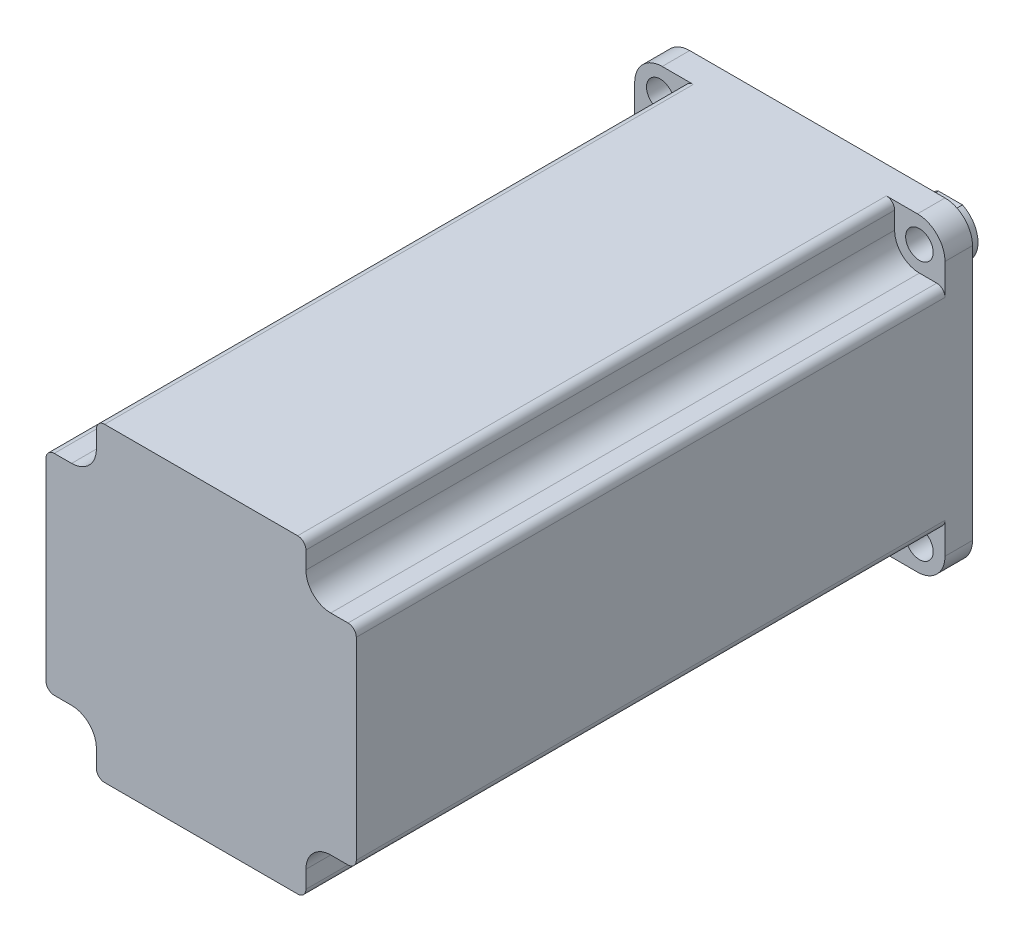
SolidWorks part; units mm, degrees
ref_plane "Front Plane" through (0, 0, 0) normal (0, 0, 1) x (1, 0, 0)
ref_plane "Top Plane" through (0, 0, 0) normal (0, 1, 0) x (1, 0, 0)
ref_plane "Right Plane" through (0, 0, 0) normal (1, 0, 0) x (0, 0, -1)
sketch "Sketch1" plane through (0, 0, 0) normal (0, 0, 1) x (1, 0, 0)
  line L1 (-28.2, -28.2) -> (28.2, -28.2)
  line L2 (-28.2, -28.2) -> (-28.2, 28.2)
  line L3 (-28.2, 28.2) -> (28.2, 28.2)
  line L4 (28.2, -28.2) -> (28.2, 28.2)
  line L5 (-28.2, -28.2) -> (28.2, 28.2) construction
  line L6 (-28.2, 28.2) -> (28.2, -28.2) construction
  line L7 (-23.55, -23.55) -> (23.55, -23.55) construction
  line L8 (-23.55, -23.55) -> (-23.55, 23.55) construction
  line L9 (-23.55, 23.55) -> (23.55, 23.55) construction
  line L10 (23.55, -23.55) -> (23.55, 23.55) construction
  line L11 (-23.55, -23.55) -> (23.55, 23.55) construction
  line L12 (-23.55, 23.55) -> (23.55, -23.55) construction
  circle A0 centre (0, 0) radius 19.05
  circle A1 centre (-23.55, 23.55) radius 2.5
  circle A2 centre (23.55, 23.55) radius 2.5
  circle A3 centre (23.55, -23.55) radius 2.5
  circle A4 centre (-23.55, -23.55) radius 2.5
  circle A5 centre (0, 0) radius 5
  point P0 (0, 0)
  point P6 (0, 0)
  dimension "D1" = 38.1
  dimension "D6" = 10
  dimension "D2" = 56.4
  dimension "D3" = 56.4
  dimension "D4" = 47.1
  dimension "D5" = 47.1
extrude "Boss-Extrude1" add sketch "Sketch1" along normal blind 112 contours L1 L4 L3 L2 A4 A3 A2 A1 A0 | A0 A5 | A5 region at (-27.4024, 0, 0) region at (-18.5112, 0, 0) region at (0, 0, 0)
extrude "Boss-Extrude2" add sketch "Sketch1<3>" against normal blind 1.6 contours A0 A5 | A5 region at (-18.5112, 0, 0) region at (0, 0, 0)
sketch "Sketch1<3>" plane through (0, 0, 0) normal (0, 0, 1) x (1, 0, 0) same geometry as "Sketch1"
fillet "Fillet1" radius 5 4 edges at (-28.2, 28.2, 56) (-28.2, -28.2, 56) (28.2, -28.2, 56) (28.2, 28.2, 56)
sketch "Sketch2" plane through (0, 0, 112) normal (0, 0, 1) x (1, 0, 0)
  line L0 (-23.55, 19.045) -> (-31.6168, 19.045)
  line L1 (-31.6168, 19.045) -> (-31.6168, 32.3658)
  line L2 (-31.6168, 32.3658) -> (-19.045, 32.3658)
  line L3 (-19.045, 32.3658) -> (-19.045, 23.55)
  line L4 (19.045, 23.55) -> (19.045, 31.6168)
  line L5 (19.045, 31.6168) -> (32.3658, 31.6168)
  line L6 (32.3658, 31.6168) -> (32.3658, 19.045)
  line L7 (32.3658, 19.045) -> (23.55, 19.045)
  line L8 (23.55, -19.045) -> (31.6168, -19.045)
  line L9 (31.6168, -19.045) -> (31.6168, -32.3658)
  line L10 (31.6168, -32.3658) -> (19.045, -32.3658)
  line L11 (19.045, -32.3658) -> (19.045, -23.55)
  line L12 (-19.045, -23.55) -> (-19.045, -31.6168)
  line L13 (-19.045, -31.6168) -> (-32.3658, -31.6168)
  line L14 (-32.3658, -31.6168) -> (-32.3658, -19.045)
  line L15 (-32.3658, -19.045) -> (-23.55, -19.045)
  circle A0 centre (-23.55, 23.55) radius 4.505 construction
  arc A1 (-23.55, 19.045) -> (-19.045, 23.55) centre (-23.55, 23.55) ccw
  arc A2 (19.045, 23.55) -> (23.55, 19.045) centre (23.55, 23.55) ccw
  circle A3 centre (23.55, 23.55) radius 4.505 construction
  arc A4 (23.55, -19.045) -> (19.045, -23.55) centre (23.55, -23.55) ccw
  circle A5 centre (23.55, -23.55) radius 4.505 construction
  arc A6 (-19.045, -23.55) -> (-23.55, -19.045) centre (-23.55, -23.55) ccw
  circle A7 centre (-23.55, -23.55) radius 4.505 construction
  point P36 (0, 0)
  dimension "D1" = 4
extrude "Cut-Extrude1" cut sketch "Sketch2" against normal blind 107
fillet "Fillet2" radius 1.5 8 edges at (-28.2, -19.045, 58.5) (-19.045, -28.2, 58.5) (19.045, -28.2, 58.5) (28.2, -19.045, 58.5) (28.2, 19.045, 58.5) (19.045, 28.2, 58.5) (-19.045, 28.2, 58.5) (-28.2, 19.045, 58.5)
extrude "Boss-Extrude3" add sketch "Sketch1<4>" against normal blind 24.2 contours A5 region at (0, 0, 0)
sketch "Sketch1<4>" plane through (0, 0, 0) normal (0, 0, 1) x (1, 0, 0) same geometry as "Sketch1"
sketch "Sketch3" plane through (0, 0, -24.2) normal (0, 0, -1) x (-1, 0, 0)
  line L0 (-2.1794, 4.5) -> (2.1794, 4.5)
  line L1 (0, 0) -> (2.0421, 0) construction
  line L2 (-2.1794, 4.5) -> (-2.1794, 5.3542)
  line L3 (-2.1794, 5.3542) -> (2.1794, 5.3542)
  line L4 (2.1794, 5.3542) -> (2.1794, 4.5)
  circle A0 centre (0, 0) radius 5 construction
  dimension "D1" = 4.5
extrude "Cut-Extrude2" cut sketch "Sketch3" against normal blind 20
